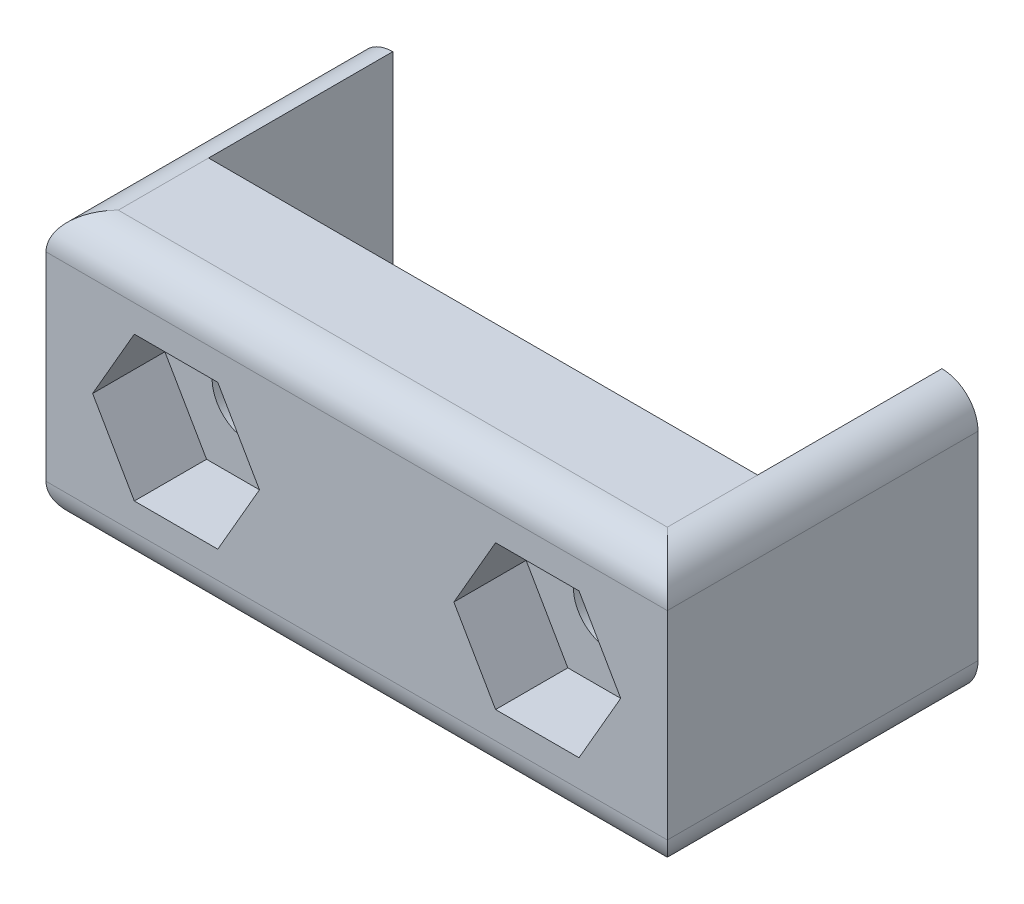
SolidWorks part; units mm, degrees
ref_plane "Front Plane" through (0, 0, 0) normal (0, 0, 1) x (1, 0, 0)
ref_plane "Top Plane" through (0, 0, 0) normal (0, 1, 0) x (1, 0, 0)
ref_plane "Right Plane" through (0, 0, 0) normal (1, 0, 0) x (0, 0, -1)
sketch "Sketch1" plane through (0, 0, 0) normal (0, 1, 0) x (1, 0, 0)
  line L0 (-21.844, 0) -> (21.844, 0)
  line L1 (-19.304, 12.954) -> (19.304, 12.954)
  line L2 (-19.304, 12.954) -> (-19.304, -12.954)
  line L3 (-19.304, -12.954) -> (19.304, -12.954)
  line L4 (19.304, 12.954) -> (19.304, -12.954)
  line L5 (-19.304, 12.954) -> (19.304, -12.954) construction
  line L6 (-19.304, -12.954) -> (19.304, 12.954) construction
  line L7 (-21.844, 21.844) -> (21.844, 21.844)
  line L8 (-21.844, 21.844) -> (-21.844, -21.844)
  line L9 (-21.844, -21.844) -> (21.844, -21.844)
  line L10 (21.844, 21.844) -> (21.844, -21.844)
  line L11 (-21.844, 21.844) -> (21.844, -21.844) construction
  line L12 (-21.844, -21.844) -> (21.844, 21.844) construction
  point P0 (0, 0)
  point P6 (0, 0)
  dimension "D1" = 38.608
  dimension "D2" = 25.908
  dimension "D3" = 43.688
  dimension "D4" = 43.688
extrude "Boss-Extrude1" add sketch "Sketch1" along normal blind 19.05 contours L10 L0 L4 L3 L2 L8 L9 region at (0, 0, 15.8166)
sketch "Sketch2" plane through (0, 0, 21.844) normal (0, 0, 1) x (1, 0, 0)
  line L0 (-21.844, 9.525) -> (21.844, 9.525) construction
  line L1 (-21.844, 19.05) -> (-21.844, 0) construction
  line L2 (21.844, 19.05) -> (21.844, 0) construction
  line L3 (-21.844, 0) -> (21.844, 0) construction
  circle A0 centre (-12.7, 9.525) radius 2.54
  circle A1 centre (12.7, 9.525) radius 2.54
  point P10 (0, 0)
  point P11 (0, 0)
  point P12 (0, 0)
  point P15 (0, 0)
  dimension "D1" = 5.08
  dimension "D2" = 5.08
  dimension "D3" = 12.7
  dimension "D4" = 12.7
extrude "Cut-Extrude1" cut sketch "Sketch2" against normal through all
sketch "Sketch3" plane through (0, 0, 21.844) normal (0, 0, 1) x (1, 0, 0)
  line L1 (-9.7671, 4.445) -> (-6.8341, 9.525)
  line L2 (-6.8341, 9.525) -> (-9.7671, 14.605)
  line L3 (-9.7671, 14.605) -> (-15.6329, 14.605)
  line L4 (-15.6329, 14.605) -> (-18.5659, 9.525)
  line L5 (-18.5659, 9.525) -> (-15.6329, 4.445)
  line L6 (-15.6329, 4.445) -> (-9.7671, 4.445)
  line L7 (15.6329, 4.445) -> (18.5659, 9.525)
  line L8 (18.5659, 9.525) -> (15.6329, 14.605)
  line L9 (15.6329, 14.605) -> (9.7671, 14.605)
  line L10 (9.7671, 14.605) -> (6.8341, 9.525)
  line L11 (6.8341, 9.525) -> (9.7671, 4.445)
  line L12 (9.7671, 4.445) -> (15.6329, 4.445)
  circle A4 centre (-12.7, 9.525) radius 5.08 construction
  circle A5 centre (-12.7, 9.525) radius 2.54 construction
  circle A6 centre (12.7, 9.525) radius 5.08 construction
  dimension "D1" = 10.16
  dimension "D2" = 10.16
extrude "Cut-Extrude2" cut sketch "Sketch3" against normal blind 5.08
fillet "Fillet1" radius 2.54 3 edges at (-21.844, 19.05, 10.922) (21.844, 19.05, 10.922) (0, 19.05, 21.844)
fillet "Fillet2" radius 2.54 3 edges at (-21.844, 0, 10.922) (0, 0, 21.844) (21.844, 0, 10.922)
